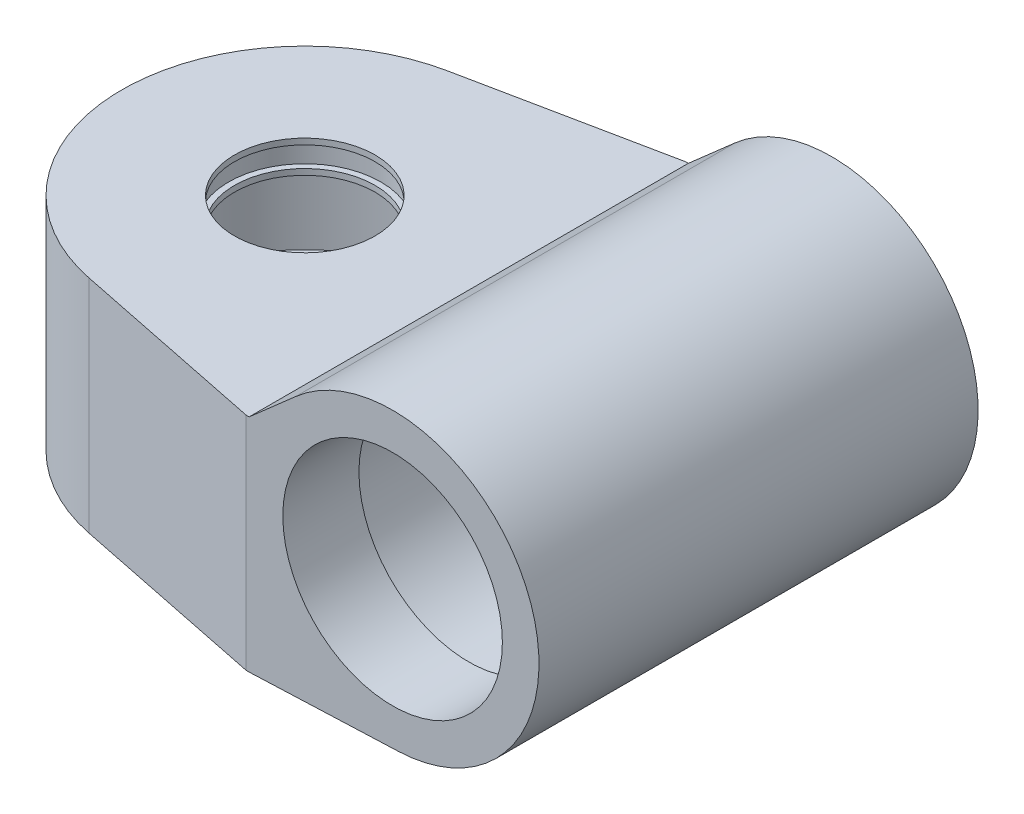
SolidWorks part; units mm, degrees
ref_plane "Front Plane" through (0, 0, 0) normal (0, 0, 1) x (1, 0, 0)
ref_plane "Top Plane" through (0, 0, 0) normal (0, 1, 0) x (1, 0, 0)
ref_plane "Right Plane" through (0, 0, 0) normal (1, 0, 0) x (0, 0, -1)
ref_axis "Joint 3 Axis" through (0, -62.75, 0) along (0, 1, 0)
sketch "Sketch2" plane through (0, 0, 0) normal (1, 0, 0) x (0, 0, -1)
  line L0 (47, -37.75) -> (62.5, -37.75)
  line L1 (62.5, -37.75) -> (62.5, 37.75)
  line L2 (62.5, 37.75) -> (24, 37.75)
  line L3 (24, 37.75) -> (24, 35.75)
  line L4 (24, 35.75) -> (26, 35.75)
  line L5 (26, 35.75) -> (26, 28.75)
  line L6 (26, 28.75) -> (24, 28.75)
  line L7 (24, 28.75) -> (24, 26.75)
  line L8 (24, 26.75) -> (42.5, 26.75)
  line L11 (47, -25.75) -> (50, -25.75)
  line L12 (50, -25.75) -> (50, -35.75)
  line L13 (50, -35.75) -> (47, -35.75)
  line L14 (47, -35.75) -> (47, -37.75)
  line L15 (47, -25.75) -> (47, -15.75)
  line L17 (53, -15.75) -> (53, 17.75)
  line L18 (0, -15.4373) -> (0, -9.583) construction
  line L19 (0, 0) -> (62.5, 0) construction
  line L20 (47, -15.75) -> (53, -15.75)
  line L21 (42.5, 26.75) -> (42.5, 17.75)
  line L22 (42.5, 17.75) -> (53, 17.75)
  dimension "D1" = 10
  dimension "D2" = 7
  dimension "D3" = 2
  dimension "D4" = 100
  dimension "D5" = 52
  dimension "D6" = 71.5
  dimension "D7" = 125
  dimension "D8" = 2
  dimension "D9" = 3
  dimension "D10" = 106
  dimension "D11" = 10
  dimension "D12" = 85
  dimension "D13" = 20
revolve "Joint 3 Boss" add sketch "Sketch2" angle 360 about L18
sketch "Sketch3" plane through (0, -25.75, 0) normal (0, -1, 0) x (1, 0, 0)
  line L0 (-47.5528, 15.4508) -> (0, 0) construction
  line L1 (0, 0) -> (-50, 0) construction
  circle A0 centre (0, 0) radius 50 construction
  circle A1 centre (-47.5528, 15.4508) radius 2
  circle A2 centre (-40.4508, 29.3893) radius 2
  circle A3 centre (-29.3893, 40.4508) radius 2
  circle A4 centre (-15.4508, 47.5528) radius 2
  circle A5 centre (0, 50) radius 2
  circle A6 centre (15.4508, 47.5528) radius 2
  circle A7 centre (29.3893, 40.4508) radius 2
  circle A8 centre (40.4508, 29.3893) radius 2
  circle A9 centre (47.5528, 15.4508) radius 2
  circle A10 centre (50, 0) radius 2
  circle A11 centre (47.5528, -15.4508) radius 2
  circle A12 centre (40.4508, -29.3893) radius 2
  circle A13 centre (29.3893, -40.4508) radius 2
  circle A14 centre (15.4508, -47.5528) radius 2
  circle A15 centre (0, -50) radius 2
  circle A16 centre (-15.4508, -47.5528) radius 2
  circle A17 centre (-29.3893, -40.4508) radius 2
  circle A18 centre (-40.4508, -29.3893) radius 2
  circle A19 centre (-47.5528, -15.4508) radius 2
  circle A20 centre (-50, 0) radius 2
  point P45 (0, 0)
  dimension "D1" = 4
  dimension "D2" = 100
  dimension "D4" = 18
  dimension "D3" = 20
extrude "Joint 3 Gearbox Pin Holes" cut sketch "Sketch3" against normal blind 50 from offset 2.5 offset against normal yes
sketch "Sketch6" plane through (0, 0, 0) normal (0, 0, 1) x (1, 0, 0)
  line L0 (-62.5, -37.75) -> (62.5, -37.75) construction
  line L1 (0, -62.75) -> (0, 47.25) construction
  circle A0 centre (105, 14.25) radius 50
  circle A1 centre (105, 14.25) radius 37.5
  dimension "D1" = 52
  dimension "D2" = 100
  dimension "D4" = 75
  dimension "D3" = 105
extrude "Joint 4 Boss" add sketch "Sketch6" along normal mid plane 150
ref_axis "Joint 4 Axis" through (105, 14.25, 75) along (0, 0, -1)
ref_plane "Joint 4 Central Plane" through (0, 14.25, 0) normal (0, 1, 0) x (1, 0, 0)
sketch "Sketch8" plane through (0, 37.75, 0) normal (0, 1, 0) x (1, 0, 0)
  line L0 (55, 75) -> (-12.4864, 61.24)
  line L1 (55, 75) -> (55, 29.6858) construction
  line L3 (-12.4864, -61.24) -> (55, -75)
  line L4 (55, -29.6859) -> (55, -75) construction
  line L6 (-12.4864, 61.24) -> (-10.5885, 51.9315)
  line L7 (-10.5885, 51.9315) -> (0, 0) construction
  line L8 (0, 0) -> (-10.5885, -51.9315) construction
  line L9 (-10.5885, -51.9315) -> (-12.4864, -61.24)
  line L10 (155, 75) -> (55, 75) construction
  line L11 (55, 75) -> (56, 75)
  line L12 (56, 75) -> (56, -75)
  line L13 (55, -75) -> (155, -75) construction
  line L14 (56, -75) -> (55, -75)
  arc A0 (60.8667, 14.195) -> (60.8667, -14.195) centre (0, 0) ccw construction
  arc A1 (-10.5885, -51.9315) -> (-10.5885, 51.9315) centre (0, 0) ccw
  circle A2 centre (0, 0) radius 53 construction
  arc A3 (-10.5885, 51.9315) -> (-10.5885, -51.9315) centre (0, 0) ccw construction
  dimension "D1" = 1
extrude "Joint 4 Connection Boss" add sketch "Sketch8" against normal through all
sketch "Sketch9" plane through (0, 0, -75) normal (0, 0, -1) x (-1, 0, 0)
  line L0 (-106.9984, -35.71) -> (-56, -37.75)
  line L1 (-56, -37.75) -> (-56, 4.3001)
  line L2 (-56, 37.75) -> (-71.9907, 51.8051)
  line L3 (-56, 4.3001) -> (-56, 24.1999) construction
  line L4 (-56, 24.1999) -> (-56, 37.75)
  arc A0 (-56, 24.1999) -> (-56, 4.3001) centre (-105, 14.25) ccw construction
  arc A1 (-56, 24.1999) -> (-71.9907, 51.8051) centre (-105, 14.25) ccw
  arc A2 (-56, 4.3001) -> (-56, 24.1999) centre (-105, 14.25) ccw construction
  arc A3 (-71.9907, 51.8051) -> (-106.9984, -35.71) centre (-105, 14.25) ccw construction
  arc A4 (-106.9984, -35.71) -> (-56, 4.3001) centre (-105, 14.25) ccw
extrude "Joint 4 Connection Boss 2" add sketch "Sketch9" against normal through all
sketch "Sketch11" plane through (0, 14.25, 0) normal (0, 1, 0) x (1, 0, 0)
  line L0 (150, 8) -> (148, 8)
  line L8 (148, 1) -> (150, 1)
  line L9 (150, 1) -> (150, 8)
  line L10 (105, -75) -> (105, 75) construction
  line L11 (150, 65) -> (148, 65)
  line L13 (135, 75) -> (135, -49)
  line L15 (148, 58) -> (150, 58)
  line L16 (150, 58) -> (150, 65)
  line L17 (155, 75) -> (71.9907, 75) construction
  line L18 (148, 58) -> (146.25, 56.25)
  line L19 (146.25, 56.25) -> (146.25, 8.6345)
  line L20 (146.25, 8.6345) -> (148, 8)
  line L21 (135, 75) -> (146.25, 75)
  line L22 (146.25, 75) -> (146.25, 66.75)
  line L23 (146.25, 66.75) -> (148, 65)
  line L24 (148, 1) -> (146.25, -3.8266)
  line L25 (146.25, -3.8266) -> (146.25, -49)
  line L26 (146.25, -49) -> (135, -49)
  dimension "D1" = 45
  dimension "D2" = 7
  dimension "D3" = 2
  dimension "D4" = 10
  dimension "D5" = 50
  dimension "D6" = 15
  dimension "D7" = 41.25
  dimension "D8" = 50
revolve "Cut-Revolve1" cut sketch "Sketch11" angle 360 about axis through (105, 14.25, 75) along (0, 0, -1)
equation "\"motorToothCount\" = 60"
equation "\"housingToothCount\" = 80"
equation "\"faceWidth\" = 10mm"
equation "\"module\" = 1"
equation "\"pressureAngle\" = 20deg"
equation "\"toothCount\" = \"housingToothCount\""
equation "\"pitchAngle\" = 360deg / \"toothCount\""
equation "\"pitchDiameter\" = \"module\" * \"toothCount\""
equation "\"pitchRadius\" = \"pitchDiameter\" / 2"
equation "\"baseDiameter\" = \"pitchDiameter\" * cos(\"pressureAngle\")"
equation "\"baseRadius\" = \"baseDiameter\" / 2"
equation "\"addendum\" = - 1.0 * \"module\""
equation "\"dedendum\" = - 1.25 * \"module\""
equation "\"rootClearance\" = - 0.25 * \"module\""
equation "\"addendumDiameter\" = \"pitchDiameter\" + 2 * \"addendum\""
equation "\"addendumRadius\" = \"addendumDiameter\" / 2"
equation "\"dedendumDiameter\" = \"pitchDiameter\" - 2 * \"dedendum\""
equation "\"dedendumRadius\" = \"dedendumDiameter\" / 2"
equation "\"rootDiameter\" = \"dedendumDiameter\" - 2 * \"rootClearance\""
equation "\"rootRadius\" = \"rootDiameter\" / 2"
equation "\"dedendumFilletRadius\" = abs(\"rootClearance\") * cos(\"pressureAngle\") * tan((90 + \"pressureAngle\") / 2)"
equation "\"alpha\" = sqr(\"pitchDiameter\"^2 - \"baseDiameter\"^2) / \"baseDiameter\" * 180 / PI - \"pressureAngle\""
equation "\"beta\" = \"pitchAngle\" / 4 - \"alpha\""
equation "\"phi\" = sqr ( \"dedendumRadius\" ^ 2 - \"baseRadius\" ^ 2 ) / \"baseRadius\""
equation "\"betaR\" = \"beta\" * PI / 180"
